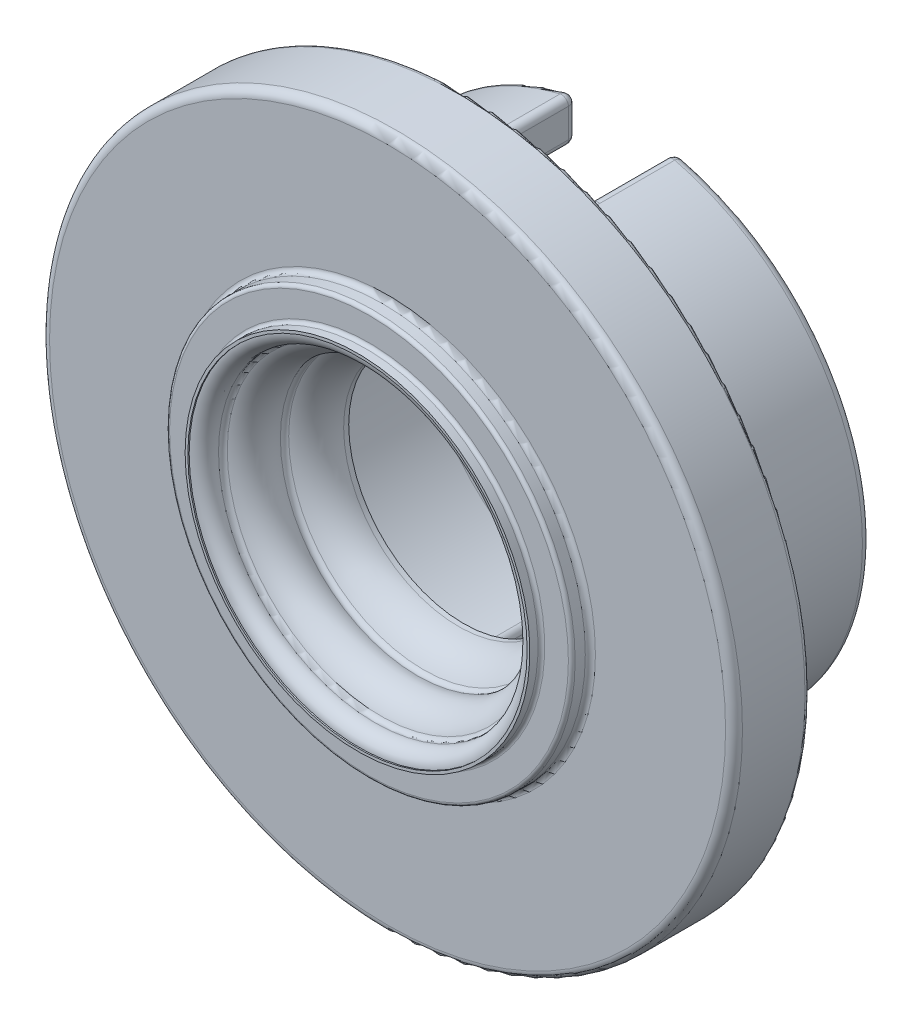
SolidWorks part; units mm, degrees
material "PE High Density"
ref_plane "Front Plane" through (0, 0, 0) normal (0, 0, 1) x (1, 0, 0)
ref_plane "Top Plane" through (0, 0, 0) normal (0, 1, 0) x (1, 0, 0)
ref_plane "Right Plane" through (0, 0, 0) normal (1, 0, 0) x (0, 0, -1)
sketch "Sketch1" plane through (0, 0, 0) normal (0, 0, 1) x (1, 0, 0)
  circle A0 centre (0, 0) radius 10.25
  circle A1 centre (0, 0) radius 3.4
  dimension "D1" = 20.5
  dimension "D2" = 6.8
extrude "Boss-Extrude1" add sketch "Sketch1" along normal blind 2.25
sketch "Sketch2" plane through (0, 0, 0) normal (0, 0, -1) x (-1, 0, 0)
  circle A0 centre (0, 0) radius 7.25
  circle A1 centre (0, 0) radius 6.02
  dimension "D1" = 14.5
  dimension "D2" = 1.23
extrude "Boss-Extrude2" add sketch "Sketch2" along normal blind 4.8
sketch "Sketch3" plane through (0, 0, 0) normal (0, 1, 0) x (1, 0, 0)
  line L0 (0, 0) -> (0, 4.8) construction
  line L1 (7.25, 4.8) -> (-7.25, 4.8) construction
  line L2 (-1.45, 4.8) -> (-1.45, 2.33)
  line L3 (6.02, 4.8) -> (-6.02, 4.8) construction
  line L4 (-10.25, -2.25) -> (10.25, -2.25) construction
  line L5 (1.45, 2.33) -> (1.45, 4.8)
  line L6 (1.45, 4.8) -> (-1.45, 4.8)
  arc A0 (-1.45, 2.33) -> (1.45, 2.33) centre (0, 2.33) ccw
  dimension "D1" = 2.9
  dimension "D2" = 3.13
extrude "Cut-Extrude1" cut sketch "Sketch3" against normal through all and the other way through all
fillet "Fillet1" radius 0.1 2 edges at (-6.02, 0, 0) (7.25, 0, 0)
fillet "Fillet2" radius 0.2 12 edges at (-1.45, -5.8428, -3.565) (1.45, -5.8428, -3.565) (-1.45, -7.1035, -3.565) (1.45, -7.1035, -3.565) (1.45, 7.1035, -3.565) (-1.45, 7.1035, -3.565) (1.45, 5.8428, -3.565) (-1.45, 5.8428, -3.565) (0.1479, -6.0182, -0.8876) (0.1541, -7.2484, -0.8882) (-0.1541, 7.2484, -0.8882) (-0.1479, 6.0182, -0.8876)
fillet "Fillet3" radius 0.25 16 edges at (-1.5262, -7.0113, -4.8) (-1.45, -6.4257, -4.8) (-1.4909, -5.8759, -4.8) (-6.02, 0, -4.8) (-1.4909, 5.8759, -4.8) (-1.45, 6.4257, -4.8) (-1.5262, 7.0113, -4.8) (1.5262, 7.0113, -4.8) (1.45, 6.4257, -4.8) (1.4909, 5.8759, -4.8) (6.02, 0, -4.8) (1.4909, -5.8759, -4.8) (1.45, -6.4257, -4.8) (1.5262, -7.0113, -4.8) (-7.25, 0, -4.8) (7.25, 0, -4.8)
fillet "Fillet4" radius 0.15 1 edges at (10.25, 0, 0)
fillet "Fillet5" radius 0.25 1 edges at (10.25, 0, 2.25)
sketch "Sketch4" plane through (0, 0, 2.25) normal (0, 0, 1) x (1, 0, 0)
  circle A0 centre (0, 0) radius 6
  circle A1 centre (0, 0) radius 3.4 construction
  circle A2 centre (0, 0) radius 3.4
  dimension "D1" = 12
extrude "Boss-Extrude3" add sketch "Sketch4" along normal offset from surface (0.55 mm away) 7.6 up to face at (4.1675, 0, -4.8)
sketch "Sketch5" plane through (0, 0, 2.8) normal (0, 0, 1) x (1, 0, 0)
  circle A0 centre (0, 0) radius 5.1
  circle A1 centre (0, 0) radius 3.4 construction
  circle A2 centre (0, 0) radius 3.4
  dimension "D1" = 10.2
extrude "Boss-Extrude4" add sketch "Sketch5" along normal offset from surface (0.34 mm away) 7.94 up to face at (4.1675, 0, -4.8)
sketch "Sketch6" plane through (0, 0, 0) normal (0, 1, 0) x (1, 0, 0)
  line L0 (0, -0.15) -> (0, -3.14)
  line L1 (-5.1, -3.14) -> (5.1, -3.14) construction
  line L2 (-5.02, -3.14) -> (-5.02, -3.1)
  line L3 (-5.1, -2.8) -> (-5.1, -3.14) construction
  line L4 (-5.02, -2.7) -> (-4.6, -0.15) construction
  line L5 (5.02, -2.7) -> (4.6, -0.15) construction
  line L6 (5.02, -3.14) -> (5.02, -3.1)
  line L8 (-5.02, -3.14) -> (5.02, -3.14)
  line L9 (3.4, -0.15) -> (-3.4, -0.15)
  line L11 (10.25, -0.15) -> (-10.25, -0.15) construction
  line L12 (-3.4, 0) -> (-3.4, -3.14) construction
  arc A0 (-5.02, -3.1) -> (-4.6739, -2.4994) centre (-5.02, -2.7) ccw
  arc A1 (-4.6739, -2.4994) -> (-4.1119, -1.2463) centre (-4.85, -1.6679) ccw
  arc A2 (-4.1119, -1.2463) -> (-3.4, -0.15) centre (-4.6, -0.15) ccw
  arc A3 (4.1119, -1.2463) -> (3.4, -0.15) centre (4.6, -0.15) cw
  arc A4 (4.6739, -2.4994) -> (4.1119, -1.2463) centre (4.85, -1.6679) cw
  arc A5 (5.02, -3.1) -> (4.6739, -2.4994) centre (5.02, -2.7) cw
  dimension "D2" = 0.04
  dimension "D3" = 0.4
  dimension "D4" = 0.85
  dimension "D5" = 1.2
  dimension "D6" = 8
  dimension "D1" = 0.08
revolve "Cut-Revolve1" cut sketch "Sketch6" angle 360 about L0 region at (-2.0523, 0, 1.7365)
fillet "Fillet6" radius 0.15 3 edges at (-4.1119, 0, 1.2463) (-4.6739, 0, 2.4994) (6, 0, 2.25)
fillet "Fillet7" radius 0.1 2 edges at (-6, 0, 2.8) (-5.1, 0, 2.8)
